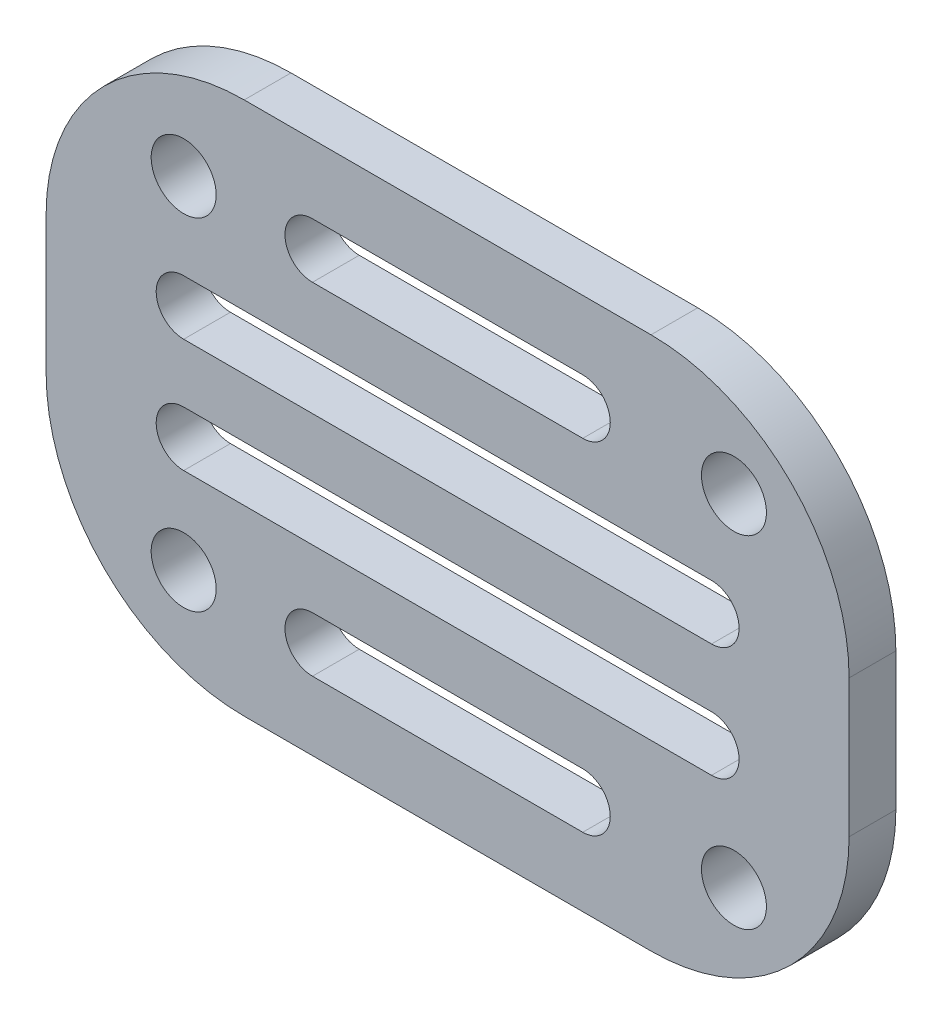
SolidWorks part; units mm, degrees
ref_plane "Front Plane" through (0, 0, 0) normal (0, 0, 1) x (1, 0, 0)
ref_plane "Top Plane" through (0, 0, 0) normal (0, 1, 0) x (1, 0, 0)
ref_plane "Right Plane" through (0, 0, 0) normal (1, 0, 0) x (0, 0, -1)
sketch "Sketch1" plane through (0, 0, 0) normal (0, 0, 1) x (1, 0, 0)
  line L0 (-12.7, -7.874) -> (12.7, -7.874) construction
  line L5 (15.338, -9.6408) -> (12.7, -7.874) construction
  line L6 (-9.906, 12.319) -> (8.8722, 12.319)
  line L7 (12.7, -7.874) -> (12.7, 7.874) construction
  line L8 (12.7, 7.874) -> (-12.7, 7.874) construction
  line L9 (-12.7, 7.874) -> (-12.7, -7.874) construction
  line L10 (-19.05, 3.175) -> (-19.05, -3.175)
  line L11 (-9.906, -12.319) -> (8.8722, -12.319)
  line L12 (18.0162, 3.175) -> (18.0162, -3.175)
  line L15 (6.9386, 0) -> (-6.9386, 0) construction
  circle A0 centre (-12.7, 7.874) radius 1.5
  circle A1 centre (-12.7, -7.874) radius 1.5
  circle A2 centre (12.7, 7.874) radius 1.5
  circle A3 centre (12.7, -7.874) radius 1.5
  arc A4 (8.8722, -12.319) -> (18.0162, -3.175) centre (8.8722, -3.175) ccw
  arc A5 (8.8722, 12.319) -> (18.0162, 3.175) centre (8.8722, 3.175) cw
  arc A6 (-9.906, 12.319) -> (-19.05, 3.175) centre (-9.906, 3.175) ccw
  arc A7 (-19.05, -3.175) -> (-9.906, -12.319) centre (-9.906, -3.175) ccw
  point P0 (0, 0)
  point P2 (-12.7, 0)
  point P3 (0, 0)
  dimension "D1" = 3
  dimension "D6" = 6.35
  dimension "D7" = 3.175
  dimension "D2" = 15.748
  dimension "D3" = 12.7
  dimension "D4" = 4.445
  dimension "D5" = 6.35
  dimension "D9" = 12.7
extrude "Boss-Extrude1" add sketch "Sketch1" along normal blind 2.159 contours A7 A4 L12 A5 A6 L10 A0 A1 A2 A3 region at (-0.5349, 0, 0)
sketch "Sketch4" plane through (0, 0, 2.159) normal (0, 0, 1) x (1, 0, 0)
  line L1 (-6.755, 7.874) -> (5.7212, 7.874) construction
  line L2 (-6.755, 9.144) -> (5.7212, 9.144)
  line L3 (-6.755, 6.604) -> (5.7212, 6.604)
  line L4 (-12.7, 2.6247) -> (11.6662, 2.6247) construction
  line L5 (-12.7, 3.8947) -> (11.6662, 3.8947)
  line L6 (-12.7, 1.3547) -> (11.6662, 1.3547)
  line L7 (-12.7, -2.6247) -> (11.6662, -2.6247) construction
  line L8 (-12.7, -1.3547) -> (11.6662, -1.3547)
  line L9 (-12.7, -3.8947) -> (11.6662, -3.8947)
  line L10 (-6.755, -7.874) -> (5.7212, -7.874) construction
  line L11 (-6.755, -6.604) -> (5.7212, -6.604)
  line L12 (-6.755, -9.144) -> (5.7212, -9.144)
  line L13 (-0.5169, 6.604) -> (-0.5169, 3.8947) construction
  line L14 (-0.5169, 1.3547) -> (-0.5169, -1.3547) construction
  line L15 (-0.5169, -3.8947) -> (-0.5169, -6.604) construction
  line L16 (-9.906, 12.319) -> (8.8722, 12.319) construction
  line L17 (-8.025, 7.874) -> (-11.2, 7.874) construction
  line L18 (18.0162, 3.175) -> (18.0162, -3.175) construction
  line L19 (-12.7, 7.874) -> (-12.7, 2.6247) construction
  arc A3 (-6.755, 9.144) -> (-6.755, 6.604) centre (-6.755, 7.874) ccw
  arc A4 (5.7212, 6.604) -> (5.7212, 9.144) centre (5.7212, 7.874) ccw
  arc A5 (-12.7, 3.8947) -> (-12.7, 1.3547) centre (-12.7, 2.6247) ccw
  arc A6 (11.6662, 1.3547) -> (11.6662, 3.8947) centre (11.6662, 2.6247) ccw
  arc A7 (-12.7, -1.3547) -> (-12.7, -3.8947) centre (-12.7, -2.6247) ccw
  arc A8 (11.6662, -3.8947) -> (11.6662, -1.3547) centre (11.6662, -2.6247) ccw
  arc A9 (-6.755, -6.604) -> (-6.755, -9.144) centre (-6.755, -7.874) ccw
  arc A10 (5.7212, -9.144) -> (5.7212, -6.604) centre (5.7212, -7.874) ccw
  circle A13 centre (-12.7, 7.874) radius 1.5 construction
  point P4 (-0.5169, 7.874)
  point P9 (-0.5169, 2.6247)
  point P16 (-0.5169, -2.6247)
  point P23 (-0.5169, -7.874)
  point P40 (-0.5169, 12.319)
  point P49 (-0.5169, 0)
  point P52 (18.0162, 0)
  dimension "D2" = 1.27
  dimension "D3" = 3.175
  dimension "D1" = 3.175
extrude "Cut-Extrude1" cut sketch "Sketch4" against normal through all
